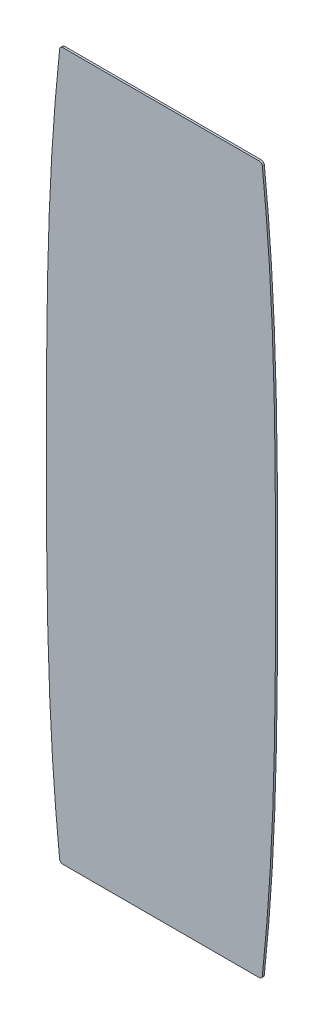
SolidWorks part; units mm, degrees
ref_plane "Front" through (0, 0, 0) normal (0, 0, 1) x (1, 0, 0)
ref_plane "Top" through (0, 0, 0) normal (0, 1, 0) x (1, 0, 0)
ref_plane "Right" through (0, 0, 0) normal (1, 0, 0) x (0, 0, -1)
sketch "Sketch1" plane through (0, 0, 0) normal (0, 0, 1) x (1, 0, 0)
  line L4 (-23.7959, -85.8) -> (23.7959, -85.8)
  line L5 (23.7959, 85.8) -> (-23.7959, 85.8)
  line L6 (-23.7959, -85.8) -> (23.7959, -85.8)
  line L7 (23.7959, 85.8) -> (-23.7959, 85.8)
  arc A8 (-24.5914, -85.0845) -> (-23.7959, -85.8) centre (-23.7959, -85) ccw
  arc A9 (23.7959, -85.8) -> (24.5914, -85.0845) centre (23.7959, -85) ccw
  arc A10 (24.5914, 85.0845) -> (23.7959, 85.8) centre (23.7959, 85) ccw
  arc A11 (-23.7959, 85.8) -> (-24.5914, 85.0845) centre (-23.7959, 85) ccw
  arc A12 (-24.5914, -85.0845) -> (-23.7959, -85.8) centre (-23.7959, -85) ccw
  arc A13 (23.7959, -85.8) -> (24.5914, -85.0845) centre (23.7959, -85) ccw
  arc A14 (24.5914, 85.0845) -> (23.7959, 85.8) centre (23.7959, 85) ccw
  arc A15 (-23.7959, 85.8) -> (-24.5914, 85.0845) centre (-23.7959, 85) ccw
  spline S8 degree 3 poles (-1813.6816, 775.3598) (38.2333, 514.2293) (-30.0727, 246.34) (-27.6629, -28.4006) (-27.5516, -35.4997) (-27.1348, -49.6946) (-26.8273, -56.7856) (-26.1559, -67.4085) (-25.8975, -70.9473) (6.4902, -456.0387) (490.043, -808.3332) (1630.7339, -1118.0367) knots -9.173904 -9.173904 -9.173904 -9.173904 0.25 0.25 0.5 0.5 0.75 0.75 0.875 0.875 14.362474 14.362474 14.362474 14.362474 only from (-27.8, 0) to (-24.5914, -85.0845)
  spline S9 degree 3 poles (-1805.145, -773.4019) (-243.2141, -617.0736) (8.2656, -350.3027) (26.8287, -56.7783) (27.1351, -49.686) (27.5518, -35.4924) (27.663, -28.3946) (30.0742, 246.5954) (-38.347, 515.2438) (1818.5454, 763.3075) knots -9.855908 -9.855908 -9.855908 -9.855908 0.25 0.25 0.5 0.5 0.75 0.75 10.184999 10.184999 10.184999 10.184999 only from (24.5914, -85.0845) to (27.8, 0)
  spline S10 degree 3 poles (1813.6816, -775.3598) (-38.2333, -514.2293) (30.0727, -246.34) (27.6629, 28.4006) (27.5516, 35.4997) (27.1348, 49.6946) (26.8273, 56.7856) (26.1559, 67.4085) (25.8975, 70.9473) (-6.4902, 456.0387) (-490.043, 808.3332) (-1630.7339, 1118.0367) knots -9.173904 -9.173904 -9.173904 -9.173904 0.25 0.25 0.5 0.5 0.75 0.75 0.875 0.875 14.362474 14.362474 14.362474 14.362474 only from (27.8, 0) to (24.5914, 85.0845)
  spline S11 degree 3 poles (1805.145, 773.4019) (243.2141, 617.0736) (-8.2656, 350.3027) (-26.8287, 56.7783) (-27.1351, 49.686) (-27.5518, 35.4924) (-27.663, 28.3946) (-30.0742, -246.5954) (38.347, -515.2438) (-1818.5454, -763.3075) knots -9.855908 -9.855908 -9.855908 -9.855908 0.25 0.25 0.5 0.5 0.75 0.75 10.184999 10.184999 10.184999 10.184999 only from (-24.5914, 85.0845) to (-27.8, 0)
  spline S12 degree 3 poles (-27.8, 0) (-27.8, -7.1003) (-27.7874, -14.2005) (-27.6629, -28.4006) (-27.5516, -35.4997) (-27.1348, -49.6946) (-26.8273, -56.7856) (-26.1559, -67.4085) (-25.8975, -70.9473) (-25.3027, -78.0197) (-24.9665, -81.5533) (-24.5914, -85.0845) knots 0 0 0 0 0.25 0.25 0.5 0.5 0.75 0.75 0.875 0.875 1 1 1 1
  spline S13 degree 3 poles (24.5914, -85.0845) (25.3415, -78.024) (25.9324, -70.9502) (26.8287, -56.7783) (27.1351, -49.686) (27.5518, -35.4924) (27.663, -28.3946) (27.7874, -14.1979) (27.8, -7.099) (27.8, 0) knots 0 0 0 0 0.25 0.25 0.5 0.5 0.75 0.75 1 1 1 1
  spline S14 degree 3 poles (27.8, 0) (27.8, 7.1003) (27.7874, 14.2005) (27.6629, 28.4006) (27.5516, 35.4997) (27.1348, 49.6946) (26.8273, 56.7856) (26.1559, 67.4085) (25.8975, 70.9473) (25.3027, 78.0197) (24.9665, 81.5533) (24.5914, 85.0845) knots 0 0 0 0 0.25 0.25 0.5 0.5 0.75 0.75 0.875 0.875 1 1 1 1
  spline S15 degree 3 poles (-24.5914, 85.0845) (-25.3415, 78.024) (-25.9324, 70.9502) (-26.8287, 56.7783) (-27.1351, 49.686) (-27.5518, 35.4924) (-27.663, 28.3946) (-27.7874, 14.1979) (-27.8, 7.099) (-27.8, 0) knots 0 0 0 0 0.25 0.25 0.5 0.5 0.75 0.75 1 1 1 1
  dimension "D1" = 0.2
extrude "Boss-Extrude1" add sketch "Sketch1" along normal up to surface (0.5 mm away)
